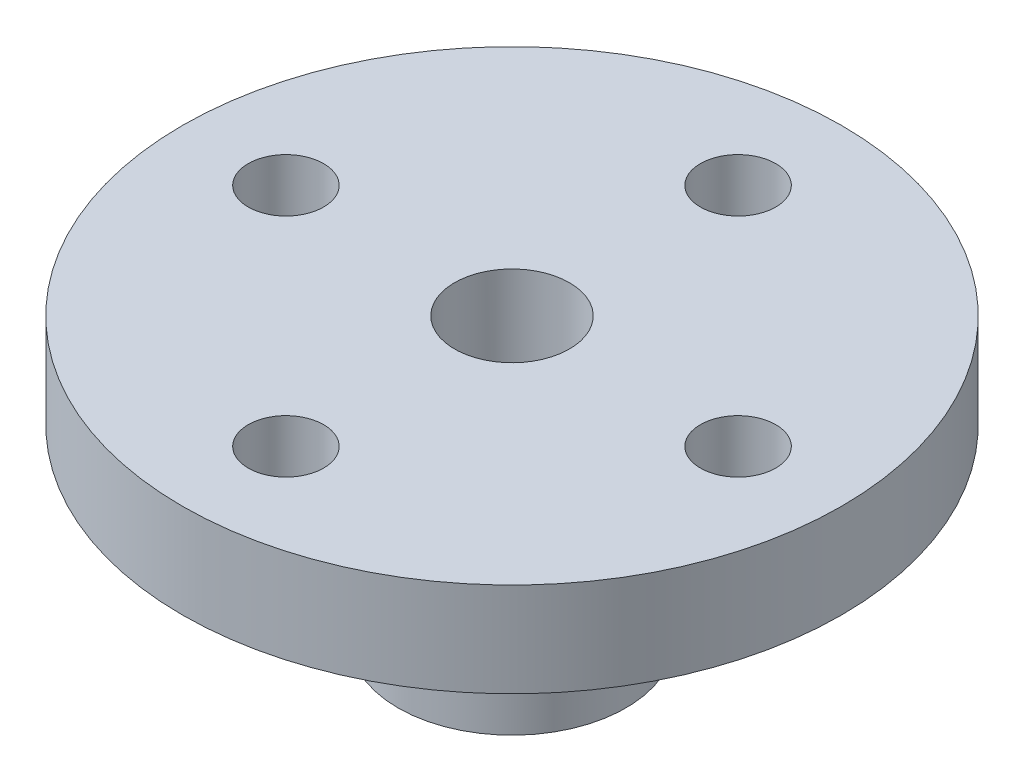
SolidWorks part; units mm, degrees
ref_plane "Front Plane" through (0, 0, 0) normal (0, 0, 1) x (1, 0, 0)
ref_plane "Top Plane" through (0, 0, 0) normal (0, 1, 0) x (1, 0, 0)
ref_plane "Right Plane" through (0, 0, 0) normal (1, 0, 0) x (0, 0, -1)
sketch "Sketch1" plane through (0, 0, 0) normal (0, 1, 0) x (1, 0, 0)
  circle A0 centre (0, 0) radius 3.05
  circle A1 centre (0, 0) radius 6.05
  dimension "D1" = 6.1
  dimension "D2" = 3
extrude "Boss-Extrude1" add sketch "Sketch1" along normal blind 10
sketch "Sketch2" plane through (0, 10, 0) normal (0, 1, 0) x (1, 0, 0)
  circle A0 centre (0, 0) radius 17.5
  dimension "D1" = 35
extrude "Boss-Extrude2" add sketch "Sketch2" along normal blind 5
sketch "Sketch3" plane through (0, 10, 0) normal (0, -1, 0) x (1, 0, 0)
  circle A0 centre (12, 0) radius 2
  circle A1 centre (0, -12) radius 2
  circle A2 centre (-12, 0) radius 2
  circle A3 centre (0, 12) radius 2
  point P11 (0, 0)
  dimension "D1" = 4
  dimension "D3" = 12
  dimension "D2" = 4
extrude "Cut-Extrude1" cut sketch "Sketch3" against normal blind 5
sketch "Sketch4" plane through (0, 0, 0) normal (1, 0, 0) x (0, 0, -1)
  circle A0 centre (0, 4.9164) radius 1.5
  dimension "D1" = 3
extrude "Cut-Extrude2" cut sketch "Sketch4" against normal through all both and the other way through all
sketch "Sketch6" plane through (0, 10, 0) normal (0, -1, 0) x (-1, 0, 0)
  circle A0 centre (0, 0) radius 3.05
extrude "Cut-Extrude3" cut sketch "Sketch6" against normal blind 5
